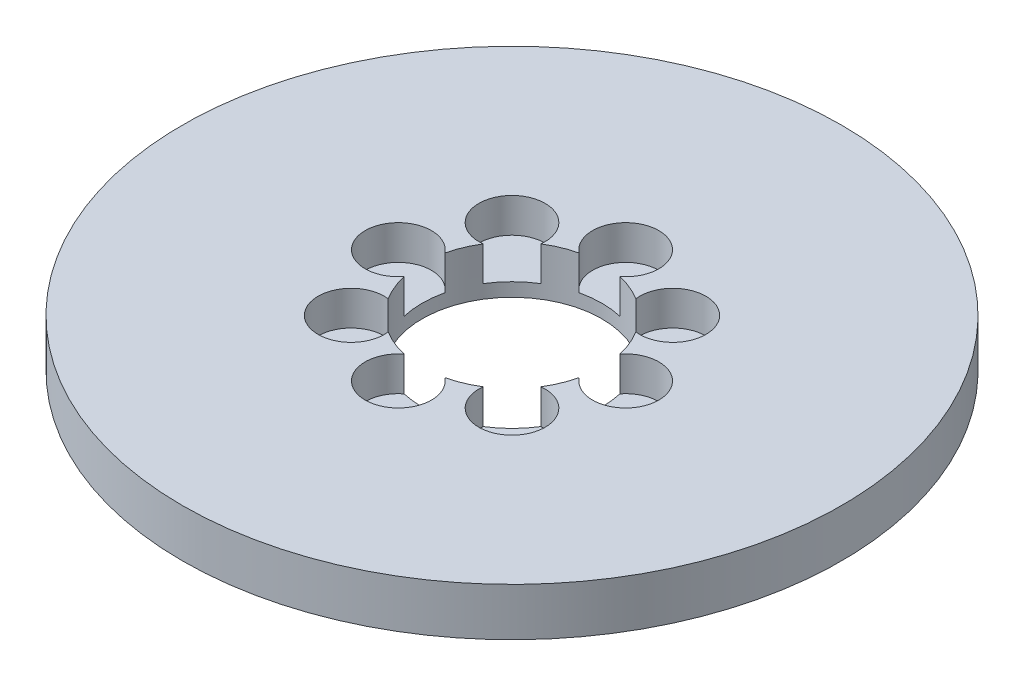
SolidWorks part; units mm, degrees
ref_plane "Front Plane" through (0, 0, 0) normal (0, 0, 1) x (1, 0, 0)
ref_plane "Top Plane" through (0, 0, 0) normal (0, 1, 0) x (1, 0, 0)
ref_plane "Right Plane" through (0, 0, 0) normal (1, 0, 0) x (0, 0, -1)
sketch "Sketch1" plane through (0, 0, 0) normal (0, 1, 0) x (1, 0, 0)
  circle A0 centre (0, 0) radius 27.5
  dimension "FLANGE_OD" = 55
extrude "Boss-Extrude1" add sketch "Sketch1" along normal blind 4
sketch "Sketch2" plane through (0, 0, 0) normal (0, 1, 0) x (1, 0, 0)
  circle A0 centre (0, 0) radius 7.5
  dimension "BORE_D" = 15
extrude "Cut-Extrude1" cut sketch "Sketch2" along normal through all
sketch "Sketch3" plane through (0, 4, 0) normal (0, 1, 0) x (1, 0, 0)
  circle A0 centre (0, 0) radius 9.4868 construction
  circle A1 centre (-9.4868, 0) radius 2.7654
  dimension "BOLT_D" = 5.5308
  dimension "BOLT_PCD" = 18.9737
extrude "Cut-Extrude2" cut sketch "Sketch3" against normal blind 2.8725
pattern_circular "CirPattern1" count 8 over 360 about axis through (0, 0, 0) along (0, 1, 0) of "Cut-Extrude2"
